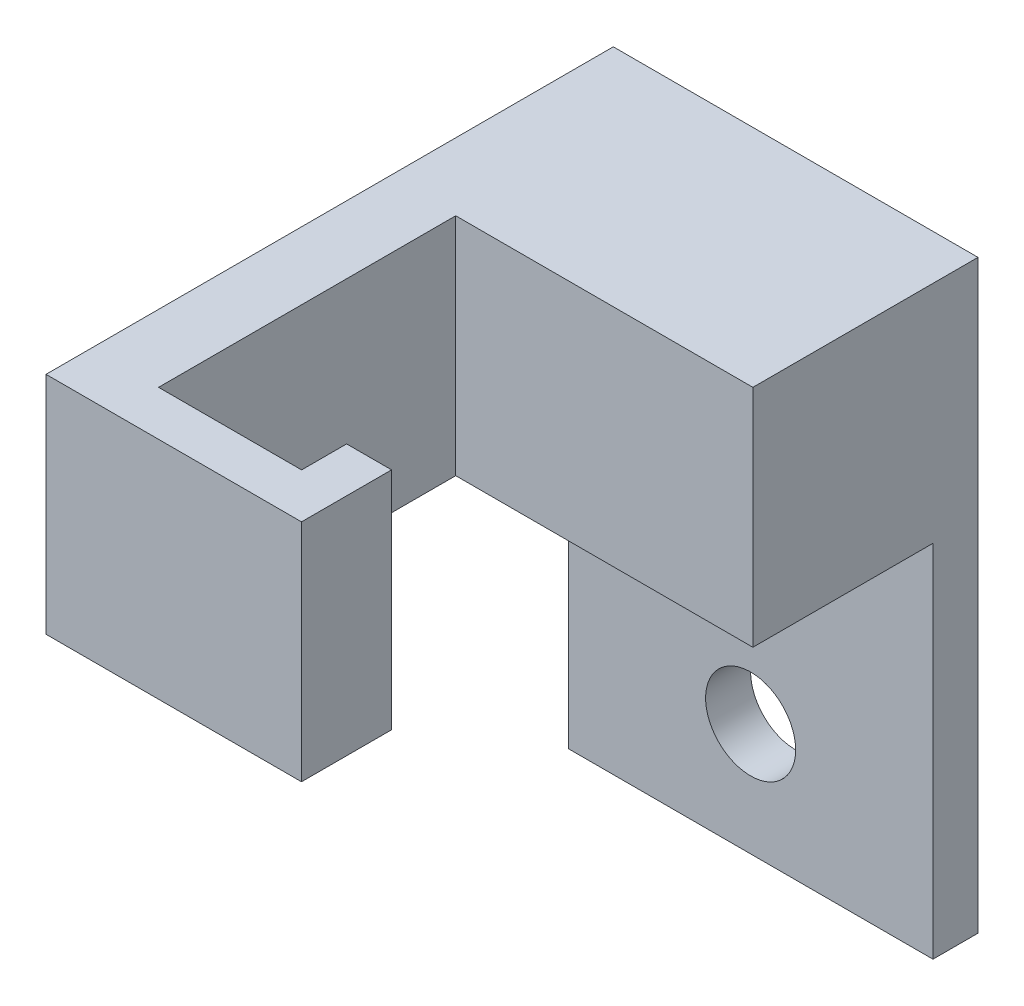
SolidWorks part; units mm, degrees
ref_plane "Front Plane" through (0, 0, 0) normal (0, 0, 1) x (1, 0, 0)
ref_plane "Top Plane" through (0, 0, 0) normal (0, 1, 0) x (1, 0, 0)
ref_plane "Right Plane" through (0, 0, 0) normal (1, 0, 0) x (0, 0, -1)
sketch "Sketch1" plane through (0, 0, 0) normal (0, 0, 1) x (1, 0, 0)
  line L0 (0, 62.1454) -> (0, -46.6941) construction
  line L1 (-111.1538, 0) -> (74.1933, 0) construction
  line L3 (-8.1, 13) -> (8.1, 13)
  line L4 (-8.1, 13) -> (-8.1, -13)
  line L5 (-8.1, -13) -> (8.1, -13)
  line L6 (8.1, 13) -> (8.1, -13)
  line L7 (-1, -1) -> (1, -1)
  line L8 (-1, -1) -> (-1, -3)
  line L9 (-1, -3) -> (1, -3)
  line L10 (1, -1) -> (1, -3)
  line L11 (-8.1, 13) -> (-5.1, 13)
  line L12 (-8.1, 13) -> (-8.1, 3)
  line L13 (-8.1, 3) -> (-5.1, 3)
  line L14 (-5.1, 13) -> (-5.1, 3)
  line L15 (-8.1, 13) -> (8.1, 13)
  line L16 (-8.1, 13) -> (-8.1, 3)
  line L17 (-8.1, 3) -> (8.1, 3)
  line L18 (8.1, 13) -> (8.1, 3)
  circle A0 centre (0, -8) radius 2
  dimension "D3" = 4
  dimension "D4" = 3
  dimension "D1" = 16.2
  dimension "D2" = 26
  dimension "D5" = 2
  dimension "D6" = 2
  dimension "D7" = 3
  dimension "D8" = 10
  dimension "D9" = 3
extrude "Boss-Extrude3" add sketch "Sketch1" along normal blind 2 contours L3 L14 L13 L4 L5 L6 A0 L7 L10 L9 L8 | L10 L7 L8 L9 region at (0, -4.8941, 0) region at (0, -2, 0)
extrude "Boss-Extrude4" add sketch "Sketch1<3>" along normal blind 17 contours L14 L3 L4 L13 region at (-6.6, 8, 0)
sketch "Sketch1<3>" plane through (0, 0, 0) normal (0, 0, 1) x (1, 0, 0) same geometry as "Sketch1"
extrude "Boss-Extrude5" add sketch "Sketch1<4>" against normal blind 1.5 contours L10 L7 L8 L9 region at (0, -2, 0)
sketch "Sketch1<4>" plane through (0, 0, 0) normal (0, 0, 1) x (1, 0, 0) same geometry as "Sketch1"
extrude "Boss-Extrude8" add sketch "Sketch1<6>" along normal blind 10 contours L14 L17 L6 L3 region at (1.5, 8, 0)
sketch "Sketch1<6>" plane through (0, 0, 0) normal (0, 0, 1) x (1, 0, 0) same geometry as "Sketch1"
extrude "Boss-Extrude9" add sketch "Sketch1<7>" along normal blind 25.2 contours L14 L3 L4 L13 region at (-6.6, 8, 0)
sketch "Sketch1<7>" plane through (0, 0, 0) normal (0, 0, 1) x (1, 0, 0) same geometry as "Sketch1"
sketch "Sketch4" plane through (0, 13, 0) normal (0, 1, 0) x (1, 0, 0)
  line L1 (-8.1, -25.2) -> (3.25, -25.2)
  line L2 (-8.1, -25.2) -> (-8.1, -23.2)
  line L3 (-8.1, -23.2) -> (1.2545, -23.2)
  line L4 (3.25, -25.2) -> (3.25, -22.2)
  line L5 (3.25, -25.2) -> (1.2545, -25.2)
  line L6 (3.25, -25.2) -> (3.25, -21.2)
  line L7 (3.25, -21.2) -> (1.2545, -21.2)
  line L8 (1.2545, -23.2) -> (1.2545, -21.2)
  line M13 (-5.1, -25.2) -> (-5.1, -10)
  dimension "D1" = 11.35
  dimension "D2" = 4
  dimension "D3" = 2
  dimension "D4" = 1.9955
extrude "Boss-Extrude10" add sketch "Sketch4" against normal blind 10 contours L8 L3 L1 L4 L6 L7 M13 region at (-0.3122, 13, 23.8142)
